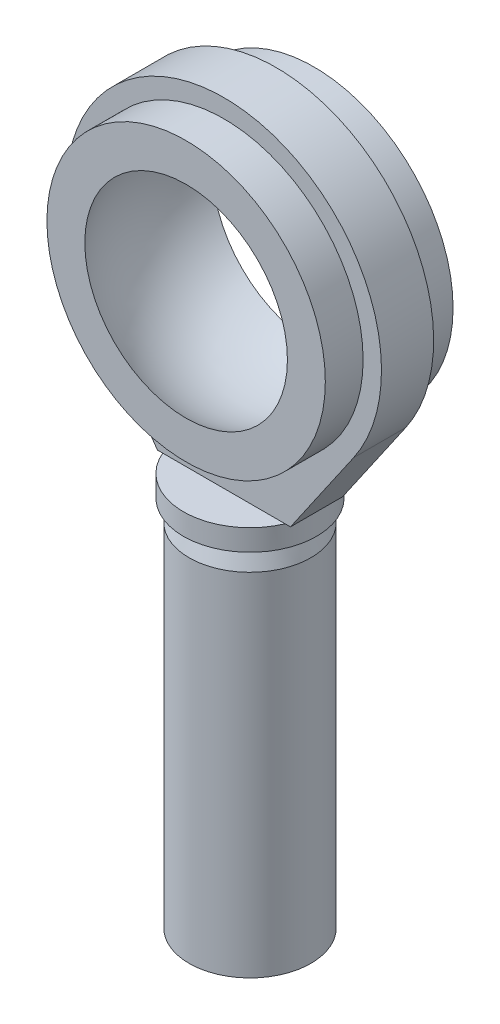
SolidWorks part; units mm, degrees
material "1023 탄소 강판(SS)"
ref_plane "정면" through (0, 0, 0) normal (0, 0, 1) x (1, 0, 0)
ref_plane "윗면" through (0, 0, 0) normal (0, 1, 0) x (1, 0, 0)
ref_plane "우측면" through (0, 0, 0) normal (1, 0, 0) x (0, 0, -1)
sketch "스케치1" plane through (0, 0, 0) normal (0, 0, 1) x (1, 0, 0)
  line L0 (0, 0) -> (0, -18.98) construction
  line L1 (-14.8, 0) -> (-14.8, -2.123)
  line L2 (14.8, 0) -> (14.8, -2.123)
  circle A1 centre (0, 0) radius 11.21
  circle A2 centre (0, 0) radius 13.075
  circle A3 centre (0, 0) radius 14.8
  arc A4 (-14.8, -2.123) -> (0, -18.98) centre (2.2, -2.123) ccw
  arc A5 (14.8, -2.123) -> (0, -18.98) centre (-2.2, -2.123) cw
  dimension "D2" = 22.42
  dimension "D3" = 26.15
  dimension "D4" = 29.6
  dimension "D6" = 17
  dimension "D5" = 18.98
extrude "보스-돌출1" add sketch "스케치1" along normal mid plane 12 contours A1 | A2 A1 region at (0, 0, 0) region at (-12.7052, 0, 0)
extrude "보스-돌출2" add sketch "스케치1<4>" along normal mid plane 4.9 contours A3 A2 region at (0, 14.3814, 0)
sketch "스케치1<4>" plane through (0, 0, 0) normal (0, 0, 1) x (1, 0, 0) same geometry as "스케치1"
ref_plane "평면1" through (0, -19, 0) normal (0, 1, 0) x (1, 0, 0)
sketch "스케치3" plane through (0, -19, 0) normal (0, 1, 0) x (1, 0, 0)
  circle A0 centre (0, 0) radius 6.25
  dimension "D1" = 12.5
extrude "보스-돌출5" add sketch "스케치3" along normal blind 2
sketch "스케치4" plane through (0, 0, 0) normal (0, 0, 1) x (1, 0, 0)
  line L0 (0, -19) -> (5.05, -19)
  line L1 (6.875, -19) -> (-6.875, -19) construction
  line L2 (0, -19) -> (0, -54)
  line L3 (0, -54) -> (5.725, -54)
  line L4 (5.725, -54) -> (5.725, -21)
  line L5 (5.05, -19) -> (5.725, -21)
  dimension "D1" = 5.05
  dimension "D2" = 35
  dimension "D3" = 5.725
  dimension "D4" = 33
revolve "회전1" add sketch "스케치4" angle 360 about L2
sketch "스케치6" plane through (0, 0, 0) normal (1, 0, 0) x (0, 0, -1)
  line L3 (11.25, 0) -> (-11.25, 0) construction
  circle A0 centre (0, 0) radius 11.25
  dimension "D1" = 22.5
revolve "컷-회전6" cut sketch "스케치6" angle 360 about L3 region at (0, 4.7746, 0)
sketch "스케치7" plane through (0, 0, 0) normal (0, 0, 1) x (1, 0, 0)
  line L0 (6.25, -17) -> (-6.25, -17) construction
  line L1 (6.25, -17) -> (-6.25, -17)
  line L2 (6.25, -17) -> (12.1808, -8.4065)
  line L3 (-6.25, -17) -> (-12.1808, -8.4065)
  circle A0 centre (0, 0) radius 14.8 construction
  arc A1 (-12.1808, -8.4065) -> (12.1808, -8.4065) centre (0, 0) ccw
extrude "보스-돌출6" add sketch "스케치7" along normal mid plane 4.9
